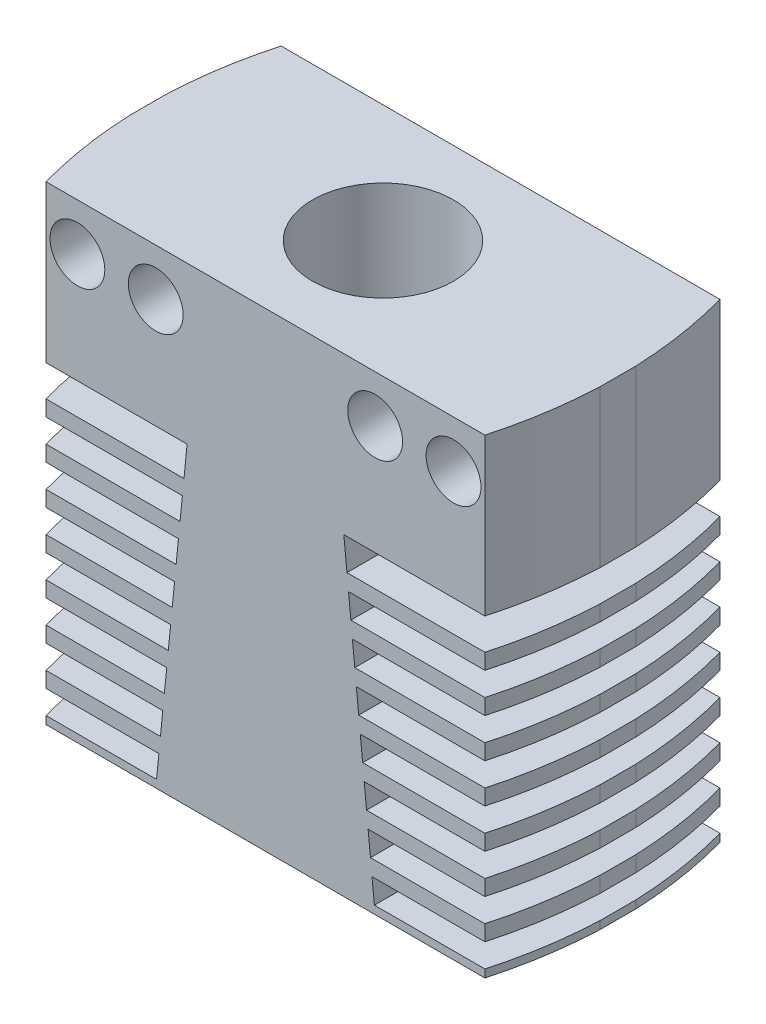
SolidWorks part; units mm, degrees
ref_plane "Спереди" through (0, 0, 0) normal (0, 0, 1) x (1, 0, 0)
ref_plane "Сверху" through (0, 0, 0) normal (0, 1, 0) x (1, 0, 0)
ref_plane "Справа" through (0, 0, 0) normal (1, 0, 0) x (0, 0, -1)
sketch "Эскиз1" plane through (0, 0, 0) normal (0, 0, 1) x (1, 0, 0)
  line L1 (0, 0) -> (30, 0)
  line L2 (0, 0) -> (0, 30)
  line L3 (0, 30) -> (30, 30)
  line L4 (30, 0) -> (30, 30)
extrude "Бобышка-Вытянуть1" add sketch "Эскиз1" along normal blind 15
hole_wizard "Диаметр отверстия Ø3.5 (3.5)1" positions "Эскиз2" profile "Эскиз3" hole size "Ø3.5" standard "ISO" end condition through all
sketch "Эскиз2" plane through (0, 0, 15) normal (0, 0, 1) x (1, 0, 0)
  line L0 (0, 30) -> (0, 0) construction
  line L1 (30, 0) -> (30, 30) construction
  line L2 (30, 30) -> (0, 30) construction
  line L3 (27, 27) -> (1.1354, 27) construction
  point P0 (3, 27)
  point P2 (8, 27)
  point P4 (22, 27)
  point P6 (27, 27)
  dimension "D1" = 3
  dimension "D2" = 3
  dimension "D3" = 3
  dimension "D4" = 5
  dimension "D5" = 5
sketch "Эскиз3" plane through (3, 27, 15) normal (1, 0, 0) x (0, -1, 0)
  line L0 (0, 0) -> (0, 15)
  line L1 (0, 15) -> (1.75, 15)
  line L2 (1.75, 15) -> (1.75, 0)
  line L5 (1.75, 0) -> (0, 0)
  line L11 (0, -6.35) -> (0, 107.95) construction
  dimension "Диаметр сквозного отверстия" = 3.5
  dimension "Глубина сквозного отверстия" = 15
sketch "Эскиз4" plane through (0, 0, 15) normal (0, 0, 1) x (1, 0, 0)
  line L0 (0, 14.5) -> (9.45, 14.5)
  line L3 (0, 20) -> (10, 20)
  line L5 (30, 30) -> (0, 30) construction
  line L6 (15, 31.0245) -> (15, -0.9819) construction
  line L7 (0, 30) -> (0, 0) construction
  line L8 (10, 20) -> (9.8, 18)
  line L11 (0, 20) -> (0, 18)
  line L12 (0, 18) -> (9.8, 18)
  line L14 (0, 17) -> (9.7, 17)
  line L15 (0, 17) -> (0, 15.5)
  line L16 (0, 15.5) -> (9.55, 15.5)
  line L18 (0, 14.5) -> (0, 13)
  line L31 (0, 13) -> (9.3, 13)
  line L33 (0, 12) -> (9.2, 12)
  line L34 (0, 12) -> (0, 10.5)
  line L35 (0, 10.5) -> (9.05, 10.5)
  line L37 (0, 9.5) -> (8.95, 9.5)
  line L38 (0, 9.5) -> (0, 8)
  line L39 (0, 8) -> (8.8, 8)
  line L41 (0, 7) -> (8.7, 7)
  line L42 (0, 7) -> (0, 5.5)
  line L43 (0, 5.5) -> (8.55, 5.5)
  line L45 (0, 4.5) -> (8.45, 4.5)
  line L46 (0, 4.5) -> (0, 3)
  line L47 (0, 3) -> (8.3, 3)
  line L49 (0, 2) -> (8.2, 2)
  line L50 (0, 2) -> (0, 0.5)
  line L51 (0, 0.5) -> (8.05, 0.5)
  line L53 (21.8, 2) -> (21.95, 0.5)
  line L54 (21.55, 4.5) -> (21.7, 3)
  line L55 (21.3, 7) -> (21.45, 5.5)
  line L56 (21.05, 9.5) -> (21.2, 8)
  line L57 (20.8, 12) -> (20.95, 10.5)
  line L58 (20.55, 14.5) -> (20.7, 13)
  line L59 (9.7, 17) -> (9.55, 15.5)
  line L60 (9.45, 14.5) -> (9.3, 13)
  line L61 (9.2, 12) -> (9.05, 10.5)
  line L62 (8.95, 9.5) -> (8.8, 8)
  line L63 (8.7, 7) -> (8.55, 5.5)
  line L64 (8.45, 4.5) -> (8.3, 3)
  line L65 (8.2, 2) -> (8.05, 0.5)
  line L66 (20.3, 17) -> (20.45, 15.5)
  line L67 (30, 0.5) -> (21.95, 0.5)
  line L68 (30, 2) -> (30, 0.5)
  line L69 (30, 2) -> (21.8, 2)
  line L70 (30, 3) -> (21.7, 3)
  line L71 (30, 4.5) -> (30, 3)
  line L72 (30, 4.5) -> (21.55, 4.5)
  line L73 (30, 5.5) -> (21.45, 5.5)
  line L74 (30, 7) -> (30, 5.5)
  line L75 (30, 7) -> (21.3, 7)
  line L76 (30, 8) -> (21.2, 8)
  line L77 (30, 9.5) -> (30, 8)
  line L78 (30, 9.5) -> (21.05, 9.5)
  line L79 (30, 10.5) -> (20.95, 10.5)
  line L80 (30, 12) -> (30, 10.5)
  line L81 (30, 12) -> (20.8, 12)
  line L82 (30, 13) -> (20.7, 13)
  line L83 (30, 14.5) -> (30, 13)
  line L84 (30, 15.5) -> (20.45, 15.5)
  line L85 (30, 17) -> (30, 15.5)
  line L86 (30, 17) -> (20.3, 17)
  line L87 (30, 18) -> (20.2, 18)
  line L88 (30, 20) -> (30, 18)
  line L89 (30, 20) -> (20, 20)
  line L90 (20, 20) -> (20.2, 18)
  line L92 (30, 14.5) -> (20.55, 14.5)
  dimension "D1" = 10
  dimension "D2" = 15
  dimension "D3" = 10
  dimension "D5" = 2
  dimension "D6" = 1
  dimension "D7" = 1.5
  dimension "D8" = 7
extrude "Вырез-Вытянуть1" cut sketch "Эскиз4" against normal through all
sketch "Эскиз5" plane through (0, 30, 0) normal (0, 1, 0) x (1, 0, 0)
  line L0 (15, 0) -> (15, -15) construction
  line L1 (30, 0) -> (0, 0) construction
  line L2 (30, -15) -> (0, -15) construction
  line L3 (30, -7.5) -> (0, -7.5) construction
  line L4 (30, -15) -> (30, 0) construction
  line L5 (0, -15) -> (0, 0) construction
  line L15 (30.335, 0) -> (30.335, -15)
  line L16 (30.335, -15) -> (29, -15)
  line L17 (30.335, 0) -> (29, 0)
  line L18 (-0.335, 0) -> (1, 0)
  line L19 (-0.335, -15) -> (1, -15)
  line L20 (-0.335, 0) -> (-0.335, -15)
  arc A0 (29, 0) -> (29, -15) centre (2.0232, -7.5) cw
  arc A1 (1, 0) -> (1, -15) centre (27.9768, -7.5) ccw
  dimension "D1" = 1
  dimension "D2" = 1
extrude "Вырез-Вытянуть2" cut sketch "Эскиз5" against normal up to surface (30 mm away) up to face at (15, 0, 7.5)
sketch "Эскиз6" plane through (0, 30, 0) normal (0, 1, 0) x (1, 0, 0)
  line L0 (15, 0) -> (15, -15) construction
  line L1 (29, 0) -> (1, 0) construction
  line L2 (29, -15) -> (1, -15) construction
  circle A0 centre (15, -7.5) radius 4.5
extrude "Вырез-Вытянуть3" cut sketch "Эскиз6" against normal blind 7
